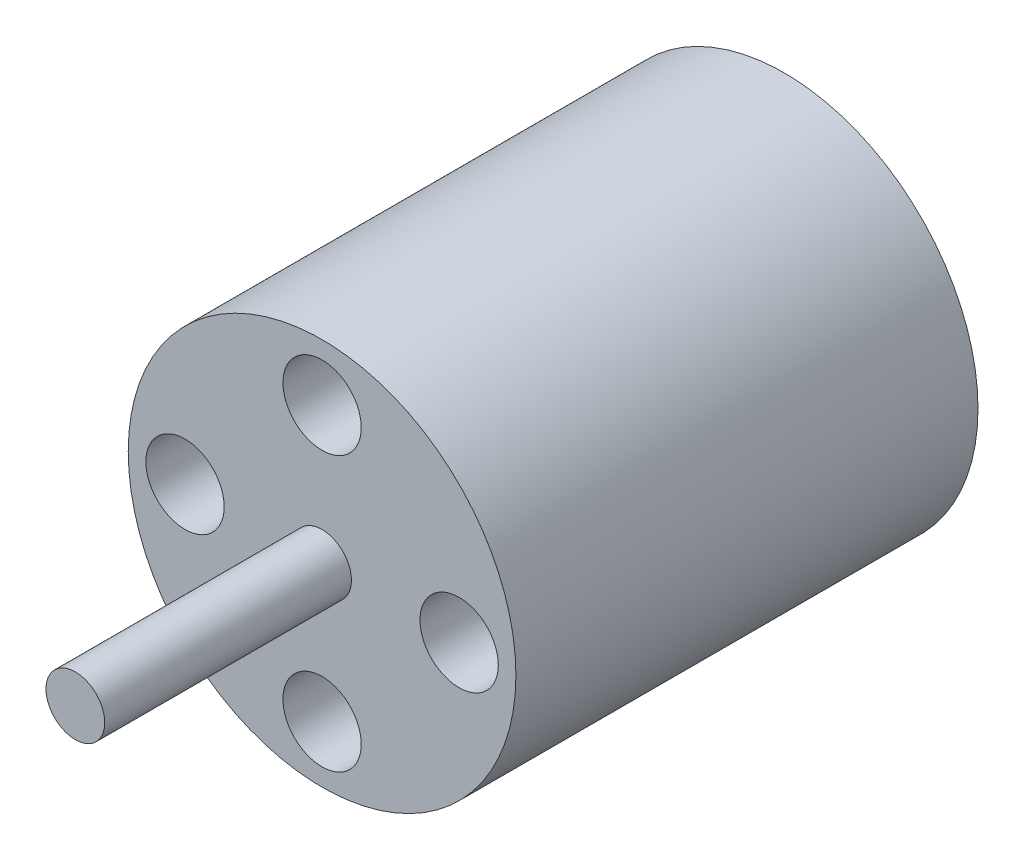
SolidWorks part; units mm, degrees
ref_plane "Front Plane" through (0, 0, 0) normal (0, 0, 1) x (1, 0, 0)
ref_plane "Top Plane" through (0, 0, 0) normal (0, 1, 0) x (1, 0, 0)
ref_plane "Right Plane" through (0, 0, 0) normal (1, 0, 0) x (0, 0, -1)
sketch "Sketch1" plane through (0, 0, 0) normal (0, 0, 1) x (1, 0, 0)
  circle A0 centre (0, 0) radius 4.95
  circle A1 centre (0, 0) radius 0.75
  circle A2 centre (0, 0) radius 3.5 construction
  circle A3 centre (0, 3.5) radius 1
  circle A4 centre (3.5, 0) radius 1
  circle A5 centre (0, -3.5) radius 1
  circle A6 centre (-3.5, 0) radius 1
  point P7 (-3.5, 0)
  point P16 (0, 0)
  dimension "D1" = 9.9
  dimension "D2" = 1.5
  dimension "D3" = 7
  dimension "D4" = 2
  dimension "D5" = 4
extrude "Boss-Extrude1" add sketch "Sketch1" along normal blind 11.8 contours A3 | A6 | A0 A6 A5 A4 A3 A1 | A4 | A5 region at (-4.81, 0, 0) region at (0, 3.5, 0) region at (3.5, 0, 0) region at (0, -3.5, 0) region at (-3.5, 0, 0)
extrude "Boss-Extrude2" add sketch "Sketch1<3>" along normal blind 18.1 contours A1 region at (0, 0, 0)
sketch "Sketch1<3>" plane through (0, 0, 0) normal (0, 0, 1) x (1, 0, 0) same geometry as "Sketch1"
extrude "Cut-Extrude1" cut sketch "Sketch1<5>" against normal blind 2 from surface contours A3 | A6 | A4 | A5 region at (0, 3.5, 0) region at (3.5, 0, 0) region at (0, -3.5, 0) region at (-3.5, 0, 0) starting at face at (0.75, 0, 11.8)
sketch "Sketch1<5>" plane through (0, 0, 0) normal (0, 0, 1) x (1, 0, 0) same geometry as "Sketch1"
